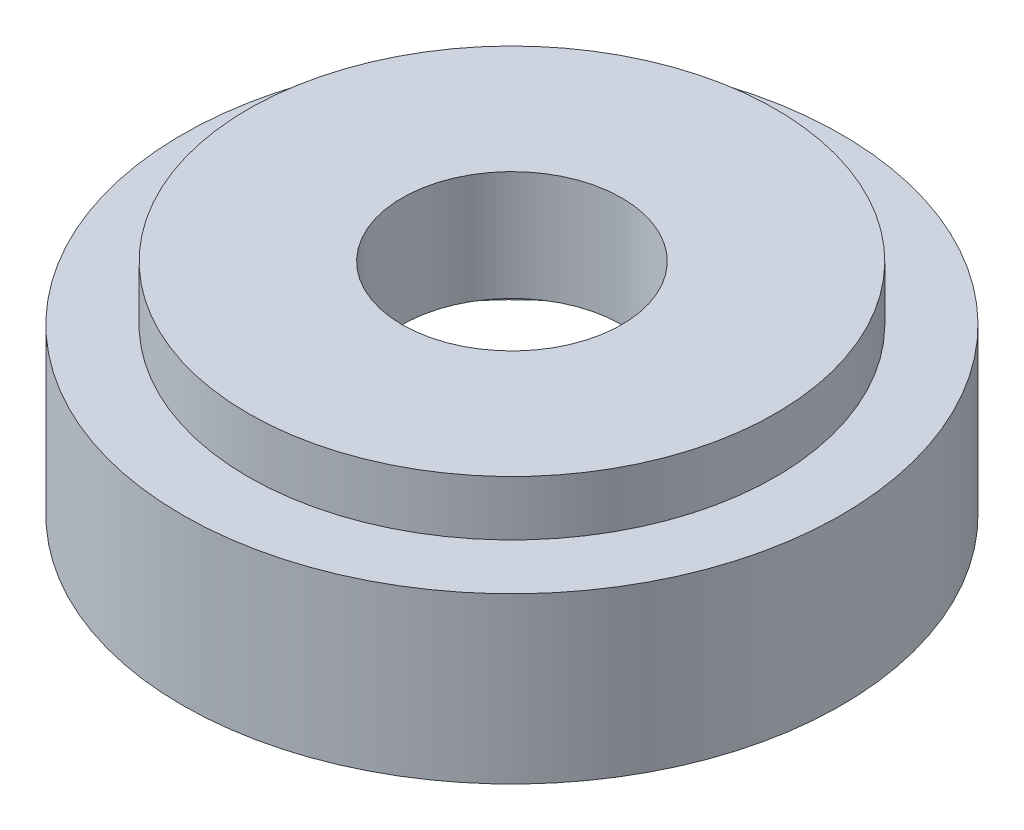
SolidWorks part; units mm, degrees
ref_plane "Front Plane" through (0, 0, 0) normal (0, 0, 1) x (1, 0, 0)
ref_plane "Top Plane" through (0, 0, 0) normal (0, 1, 0) x (1, 0, 0)
ref_plane "Right Plane" through (0, 0, 0) normal (1, 0, 0) x (0, 0, -1)
sketch "Croquis1" plane through (0, 0, 0) normal (0, 1, 0) x (1, 0, 0)
  circle A0 centre (0, 0) radius 24
  circle A1 centre (0, 0) radius 30
  circle A2 centre (0, 0) radius 10
  dimension "D1" = 48
  dimension "D2" = 60
  dimension "D3" = 20
extrude "Saliente-Extruir1" add sketch "Croquis1" along normal blind 5 contours A0 A2 region at (-23.3212, 0, 0)
extrude "Saliente-Extruir2" add sketch "Croquis1<3>" against normal blind 5 contours A1 A0 | A0 A2 region at (-23.3212, 0, 0) region at (-29.1515, 0, 0)
sketch "Croquis1<3>" plane through (0, 0, 0) normal (0, 1, 0) x (1, 0, 0) same geometry as "Croquis1"
extrude "Saliente-Extruir3" add sketch "Croquis1<4>" against normal blind 15 contours A1 A0 region at (-29.1515, 0, 0)
sketch "Croquis1<4>" plane through (0, 0, 0) normal (0, 1, 0) x (1, 0, 0) same geometry as "Croquis1"
equation "\"ID\"=48"
equation "\"D1@Croquis1\"=\"ID\""
equation "\"OD\"=60"
equation "\"D2@Croquis1\"=\"OD\""
equation "\"Dmandril\"=20"
equation "\"D3@Croquis1\"=\"Dmandril\""
